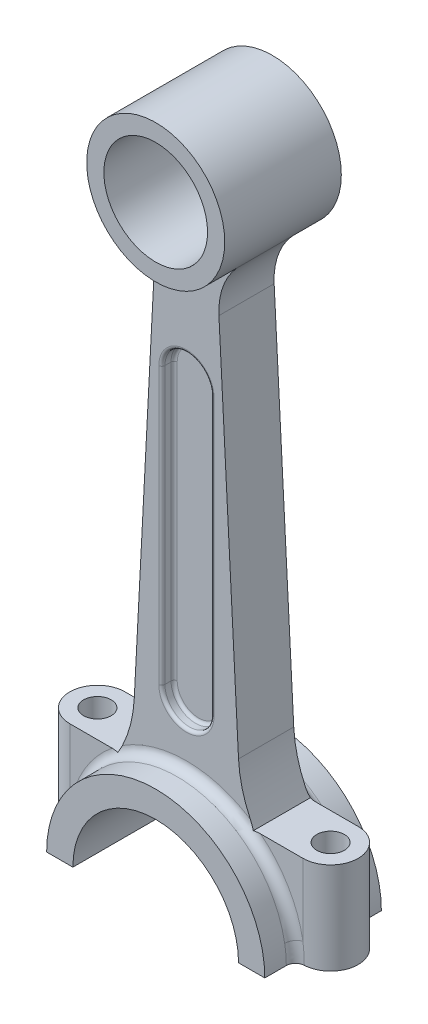
SolidWorks part; units mm, degrees
ref_plane "Front Plane" through (0, 0, 0) normal (0, 0, 1) x (1, 0, 0)
ref_plane "Top Plane" through (0, 0, 0) normal (0, 1, 0) x (1, 0, 0)
ref_plane "Right Plane" through (0, 0, 0) normal (1, 0, 0) x (0, 0, -1)
sketch "Sketch2" plane through (0, 0, 0) normal (0, 0, 1) x (1, 0, 0)
  line L0 (0, 0) -> (0, -201.2) construction
  line L1 (-10, -20.1556) -> (-17.8773, -170.4626)
  line L2 (10, -20.1556) -> (17.8773, -170.4626)
  line L3 (-35.5582, -201.2) -> (-27, -201.2)
  line L4 (27, -201.2) -> (35.5582, -201.2)
  circle A0 centre (0, 0) radius 22.5
  circle A1 centre (0, 0) radius 16.9
  arc A2 (27, -201.2) -> (-27, -201.2) centre (0, -201.2) ccw
  arc A3 (35.5582, -201.2) -> (-35.5582, -201.2) centre (0, -201.2) ccw
  dimension "D1" = 45
  dimension "D2" = 33.8
  dimension "D3" = 201.2
  dimension "D4" = 20
  dimension "D5" = 6
extrude "Boss-Extrude3" add sketch "Sketch2" along normal mid plane 38 contours A1 | A0 | A2 | A3
extrude "Boss-Extrude4" add sketch "Sketch2<5>" along normal mid plane 18 contours A0 L0 A3 L2 | L0 A0 L1 A3 region at (7.1923, -101.1161, 0) region at (-7.1923, -101.1161, 0)
sketch "Sketch2<5>" plane through (0, 0, 0) normal (0, 0, 1) x (1, 0, 0) same geometry as "Sketch2"
sketch "Sketch4" plane through (0, 0, 9) normal (0, 0, 1) x (1, 0, 0)
  line L0 (0, 0) -> (0, -187.6389) construction
  line L1 (0, -145.6) -> (0, -55.6) construction
  line L2 (-8, -145.6) -> (-8, -55.6)
  line L3 (8, -145.6) -> (8, -55.6)
  arc A0 (-8, -145.6) -> (8, -145.6) centre (0, -145.6) ccw
  arc A1 (8, -55.6) -> (-8, -55.6) centre (0, -55.6) ccw
  point P7 (0, -100.6)
  dimension "D2" = 8
  dimension "D1" = 90
extrude "Cut-Extrude1" cut sketch "Sketch4" against normal blind 4
mirror "Mirror2" about plane through (0, 0, 0) normal (0, 0, 1) of "Cut-Extrude1"
fillet "Fillet1" radius 1 16 edges at (0, -47.6, -9) (8, -100.6, -9) (0, -153.6, -9) (0, -47.6, -5) (8, -100.6, -5) (0, -153.6, -5) (0, -47.6, 9) (8, -100.6, 9) (0, -153.6, 9) (0, -47.6, 5) (8, -100.6, 5) (0, -153.6, 5) (-8, -100.6, -9) (-8, -100.6, -5) (-8, -100.6, 9) (-8, -100.6, 5)
extrude "Boss-Extrude5" add sketch "Sketch2<7>" along normal mid plane 38 contours L0 A3 L3 A2 | A3 L0 A2 L4 region at (20.0371, -181.1629, 0) region at (-20.0371, -181.1629, 0)
sketch "Sketch2<7>" plane through (0, 0, 0) normal (0, 0, 1) x (1, 0, 0) same geometry as "Sketch2"
fillet "Fillet2" radius 40 2 edges at (17.8773, -170.4626, 0) (-17.8773, -170.4626, 0)
fillet "Fillet3" radius 22.5 2 edges at (10, -20.1556, 0) (-10, -20.1556, 0)
ref_plane "Plane1" through (0, -171.2, 0) normal (0, -1, 0) x (-1, 0, 0)
sketch "Sketch7" plane through (0, -171.2, 0) normal (0, -1, 0) x (-1, 0, 0)
  line L0 (38, 0) -> (-38, 0) construction
  line L1 (38, -9) -> (-38, -9)
  line L2 (38, 9) -> (-38, 9)
  arc A0 (38, -9) -> (38, 9) centre (38, 0) ccw
  arc A1 (-38, 9) -> (-38, -9) centre (-38, 0) ccw
  point P2 (0, 0)
  dimension "D2" = 9
  dimension "D1" = 76
extrude "Boss-Extrude6" add sketch "Sketch7" along normal up to surface (30 mm away) up to face at (-31.2791, -201.2, 0)
sketch "Sketch8" plane through (0, 0, 9) normal (0, 0, 1) x (1, 0, 0)
  line L1 (-27, -201.2) -> (27, -201.2)
  line L2 (-27, -201.2) -> (27, -201.2)
  arc A1 (27, -201.2) -> (-27, -201.2) centre (0, -201.2) ccw
  arc A2 (27, -201.2) -> (-27, -201.2) centre (0, -201.2) ccw
  dimension "D1" = 0
extrude "Cut-Extrude3" cut sketch "Sketch8" against normal through all
sketch "Sketch10" plane through (0, -171.2, 0) normal (0, 1, 0) x (1, 0, 0)
  circle A0 centre (-38, 0) radius 4.5
  circle A1 centre (38, 0) radius 4.5
extrude "Cut-Extrude4" cut sketch "Sketch10" against normal through all
fillet "Fillet4" radius 3 2 edges at (0, -165.6418, -9) (0, -165.6418, 9)
